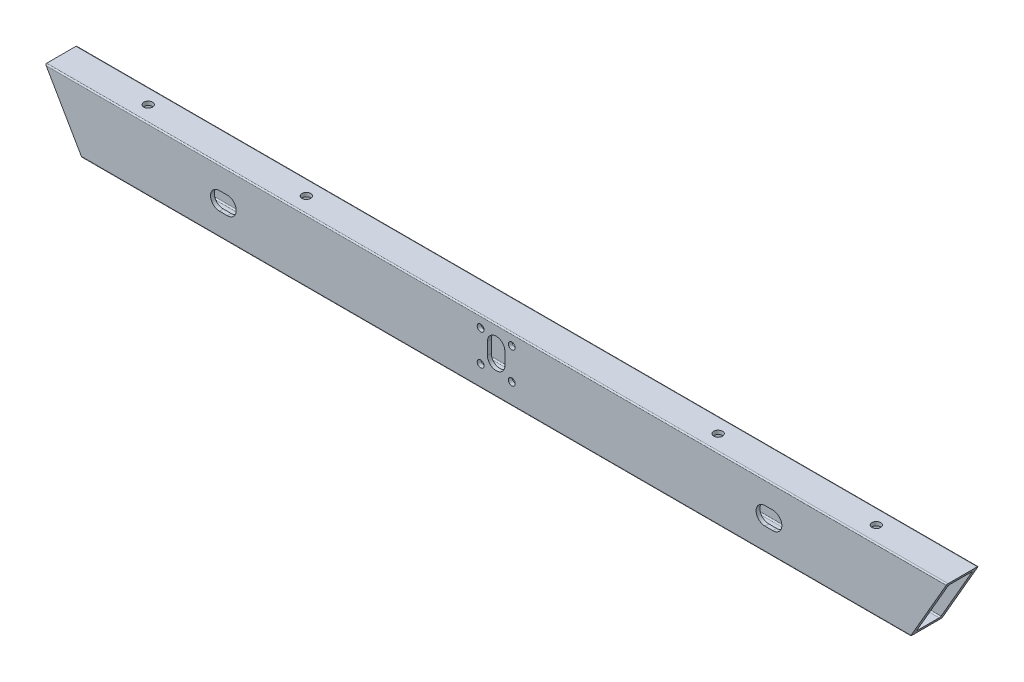
SolidWorks part; units mm, degrees
ref_plane "Front Plane" through (0, 0, 0) normal (0, 0, 1) x (1, 0, 0)
ref_plane "Top Plane" through (0, 0, 0) normal (0, 1, 0) x (1, 0, 0)
ref_plane "Right Plane" through (0, 0, 0) normal (1, 0, 0) x (0, 0, -1)
sketch "Sketch2" plane through (0, 0, 0) normal (0, 0, 1) x (1, 0, 0)
  line L0 (-332.6206, -25.4) -> (-361.95, 25.4)
  line L1 (-361.95, 25.4) -> (361.95, 25.4)
  line L3 (-332.6206, -25.4) -> (332.6206, -25.4)
  line L5 (0, 25.4) -> (0, -25.4) construction
  line L8 (332.6206, -25.4) -> (361.95, 25.4)
  point P0 (0, 0)
  point P4 (0, 0)
  point P8 (0, 25.4)
  dimension "D1" = 50.8
  dimension "D2" = 60
  dimension "D3" = 723.9
extrude "Boss-Extrude1" add sketch "Sketch2" along normal mid plane 25.4 contours L1 L8 L3 L0
sketch "Sketch3" plane through (0, 0, 0) normal (1, 0, 0) x (0, 0, -1)
  line L12 (9.652, -22.352) -> (9.652, 22.352)
  line L13 (-9.652, -22.352) -> (9.652, -22.352)
  line L14 (-9.652, 22.352) -> (-9.652, -22.352)
  line L15 (9.652, 22.352) -> (-9.652, 22.352)
  line L16 (9.652, -22.352) -> (9.652, 22.352)
  line L17 (-9.652, -22.352) -> (9.652, -22.352)
  line L18 (-9.652, 22.352) -> (-9.652, -22.352)
  line L19 (9.652, 22.352) -> (-9.652, 22.352)
  dimension "D1" = 3.048
extrude "Cut-Extrude1" cut sketch "Sketch3" against normal through all and the other way through all contours L16 L19 L18 L17
fillet "Fillet1" radius 1 8 edges at (0, 22.352, 9.652) (0, 22.352, -9.652) (0, -22.352, -9.652) (0, -22.352, 9.652) (0, -25.4, -12.7) (0, -25.4, 12.7) (0, 25.4, -12.7) (0, 25.4, 12.7)
sketch "Sketch4" plane through (0, 0, -12.7) normal (0, 0, -1) x (-1, 0, 0)
  line L1 (7, 0) -> (7, 10)
  line L2 (-7, 0) -> (-7, 10)
  arc A0 (-7, 0) -> (7, 0) centre (0, 0) ccw
  arc A1 (7, 10) -> (-7, 10) centre (0, 10) ccw
  dimension "D1" = 14
  dimension "D2" = 10
extrude "Cut-Extrude2" cut sketch "Sketch4" against normal up to next
sketch "Sketch5" plane through (0, 0, 12.7) normal (0, 0, 1) x (1, 0, 0)
  line L0 (15.875, 4) -> (-15.875, 4) construction
  line L1 (14.875, -11.875) -> (-14.875, -11.875)
  line L2 (15.875, -10.875) -> (15.875, 18.875)
  line L3 (14.875, 19.875) -> (-14.875, 19.875)
  line L4 (-15.875, -10.875) -> (-15.875, 18.875)
  arc A0 (-14.875, -11.875) -> (-15.875, -10.875) centre (-14.875, -10.875) cw
  arc A1 (14.875, -11.875) -> (15.875, -10.875) centre (14.875, -10.875) ccw
  arc A2 (15.875, 18.875) -> (14.875, 19.875) centre (14.875, 18.875) ccw
  arc A3 (-14.875, 19.875) -> (-15.875, 18.875) centre (-14.875, 18.875) ccw
  point P1 (0, 19.875)
  dimension "D2" = 1
  dimension "D1" = 31.75
  dimension "D3" = 4
extrude "Cut-Extrude3" cut sketch "Sketch5" against normal up to next
hole_wizard "M5 Clearance Hole1" positions "Sketch12" profile "Sketch7" hole size "M5" standard "ANSI Metric" end condition up to next
sketch "Sketch12" [suppressed] plane through (0, 0, -9.652) normal (0, 0, 1) x (1, 0, 0)
  line L1 (12.5, 16.5) -> (12.5, -8.5) construction
  line L2 (12.5, -8.5) -> (-12.5, -8.5) construction
  circle A5 centre (-12.5, 16.5) radius 2.1 construction
  point P0 (-12.5, 16.5)
  point P2 (12.5, 16.5)
  point P4 (12.5, -8.5)
  point P6 (-12.5, -8.5)
  point P47 (0, -8.5)
  dimension "D1" = 25
  dimension "D2" = 25
sketch "Sketch7" plane through (-12.5, 16.5, -9.652) normal (1, 0, 0) x (0, -1, 0)
  line L0 (0, 0) -> (0, 3.048)
  line L1 (0, 3.048) -> (2.75, 3.048)
  line L2 (2.75, 3.048) -> (2.75, 0)
  line L5 (2.75, 0) -> (0, 0)
  line L11 (0, -6.35) -> (0, 107.95) construction
  dimension "Thru Hole Dia." = 5.5
  dimension "Thru Hole Depth" = 3.048
sketch "Sketch9" plane through (0, 0, -12.7) normal (0, 0, -1) x (-1, 0, 0)
  line L0 (-222.25, 0) -> (-215.9, 0) construction
  line L1 (-222.25, 7.1437) -> (-215.9, 7.1437)
  line L2 (-222.25, -7.1437) -> (-215.9, -7.1437)
  line L3 (0, 13.97) -> (0, -13.97) construction
  line L4 (222.25, 0) -> (215.9, 0) construction
  line L5 (222.25, 7.1437) -> (215.9, 7.1437)
  line L6 (222.25, -7.1437) -> (215.9, -7.1437)
  arc A0 (-222.25, 7.1437) -> (-222.25, -7.1437) centre (-222.25, 0) ccw
  arc A1 (-215.9, -7.1437) -> (-215.9, 7.1437) centre (-215.9, 0) ccw
  arc A2 (222.25, 7.1437) -> (222.25, -7.1437) centre (222.25, 0) cw
  arc A3 (215.9, -7.1437) -> (215.9, 7.1437) centre (215.9, 0) cw
  point P2 (-219.075, 0)
  point P12 (219.075, 0)
  dimension "D2" = 14.2875
  dimension "D1" = 6.35
  dimension "D3" = 215.9
extrude "Wire Slots" cut sketch "Sketch9" against normal up to next
sketch "Sketch14" plane through (0, 25.4, 0) normal (0, 1, 0) x (1, 0, 0)
  line L0 (-165.35, -0.2) -> (-292.35, -0.2) construction
  line L1 (165.35, -0.2) -> (292.35, -0.2) construction
  line L4 (0, 0) -> (0, 11.7) construction
  line L5 (361.95, 11.7) -> (-361.95, 11.7) construction
  circle A0 centre (-165.35, -0.2) radius 3.5
  circle A2 centre (-292.35, -0.2) radius 3.5
  circle A8 centre (-165.35, -0.2) radius 2.75 construction
  circle A9 centre (-292.35, -0.2) radius 2.75 construction
  circle A10 centre (292.35, -0.2) radius 3.5
  circle A11 centre (165.35, -0.2) radius 3.5
  dimension "D1" = 7
  dimension "D2" = 165.3501
  dimension "D3" = 127
extrude "Plate Mounting" cut sketch "Sketch14" against normal up to next
mirror "Mirror1" about plane through (0, 0, -12.7) normal (0, 0, -1) of bodies 110 106
sketch "Sketch10" plane through (0, 0, 0) normal (1, 0, 0) x (0, 0, -1)
  line L0 (-12.7, -24.4) -> (-12.7, 24.4) construction
  line L1 (12.7, -25.4) -> (-12.7, -25.4)
  line L2 (12.7, -25.4) -> (12.7, 25.4)
  line L3 (12.7, 25.4) -> (-12.7, 25.4)
  line L4 (-12.7, -25.4) -> (-12.7, 25.4)
  line L5 (12.7, -25.4) -> (-12.7, 25.4) construction
  line L6 (12.7, 25.4) -> (-12.7, -25.4) construction
  line L7 (-11.7, 25.4) -> (11.7, 25.4) construction
  point P0 (0, 0)
extrude "Cut-Extrude5" cut sketch "Sketch10" against normal through all both and the other way through all
sketch "Sketch15" [suppressed] plane through (0, 0, 12.7) normal (0, 0, 1) x (1, 0, 0)
  circle A0 centre (279.4, 0) radius 11.75
  dimension "D1" = 23.5
  dimension "D2" = 279.4
extrude "Charging" [suppressed] cut sketch "Sketch15" against normal up to next
hole_wizard "Power" positions "Sketch19" profile "Sketch18" hole size "M16" standard "ANSI Metric" end condition up to next
sketch "Sketch19" plane through (0, 0, -38.1) normal (0, 0, -1) x (-1, 0, 0)
  point P0 (266.7, 0)
  point P4 (266.4921, -10.5277)
  dimension "D1" = 266.7
sketch "Sketch18" plane through (-266.7, 0, -38.1) normal (1, 0, 0) x (0, 1, 0)
  line L0 (0, 0) -> (0, 3.048)
  line L1 (0, 3.048) -> (8, 3.048)
  line L2 (8, 3.048) -> (8, 0)
  line L5 (8, 0) -> (0, 0)
  line L11 (0, -6.35) -> (0, 107.95) construction
  dimension "Thru Hole Dia." = 16
  dimension "Thru Hole Depth" = 3.048
equation "\"Length\"= 28.5"
equation "\"D3@Sketch2\"=\"Length\""
